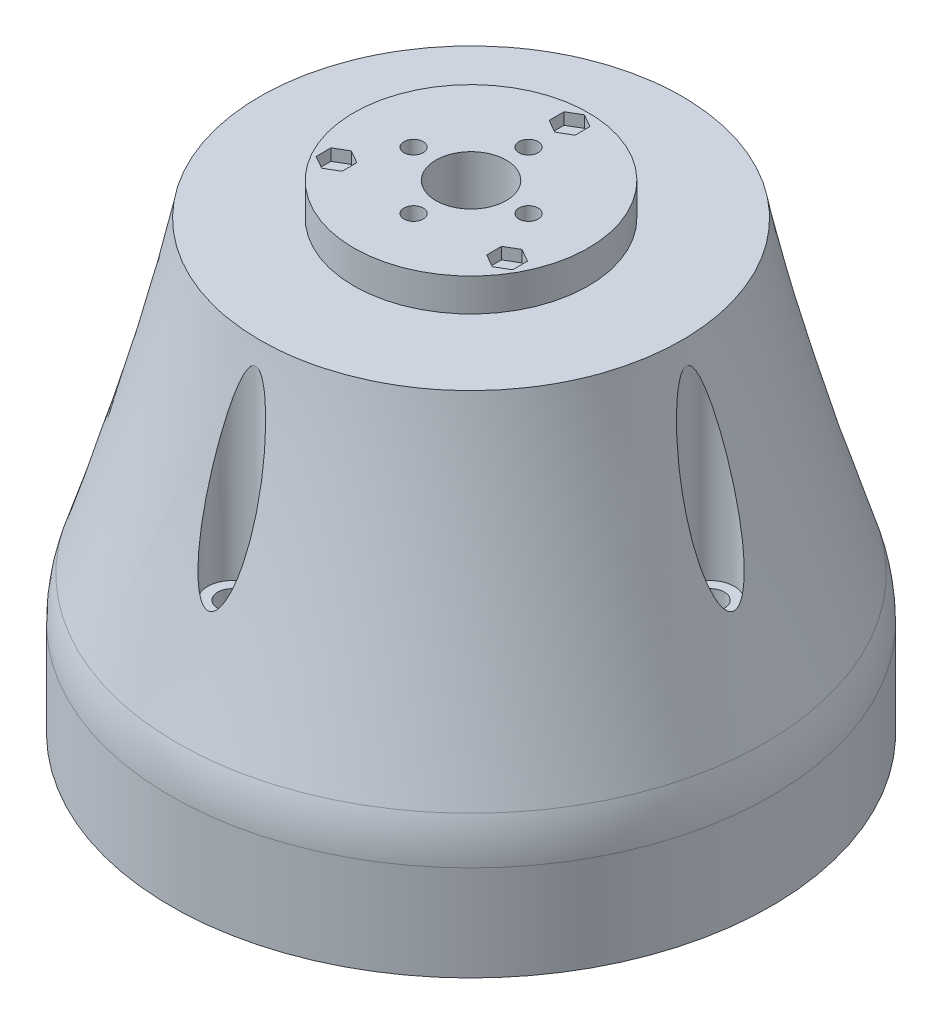
SolidWorks part; units mm, degrees
ref_plane "Front Plane" through (0, 0, 0) normal (0, 0, 1) x (1, 0, 0)
ref_plane "Top Plane" through (0, 0, 0) normal (0, 1, 0) x (1, 0, 0)
ref_plane "Right Plane" through (0, 0, 0) normal (1, 0, 0) x (0, 0, -1)
sketch "Sketch3" plane through (0, 0, 0) normal (0, 1, 0) x (1, 0, 0)
  circle A0 centre (0, 0) radius 64
  dimension "D1" = 128
extrude "Boss-Extrude1" add sketch "Sketch3" along normal blind 15
ref_plane "Plane1" through (0, 85, 0) normal (0, 1, 0) x (1, 0, 0)
sketch "Sketch4" plane through (0, 85, 0) normal (0, 1, 0) x (1, 0, 0)
  circle A0 centre (0, 0) radius 45
  dimension "D1" = 90
sketch "Sketch5" plane through (0, 15, 0) normal (0, 1, 0) x (1, 0, 0)
  circle A1 centre (0, 0) radius 64
  circle A2 centre (0, 0) radius 64
  dimension "D1" = 0
loft "Loft1" add profiles "Sketch5", "Sketch4" connector at (-2.5729, 15, 63.9483) connector at (15.8799, 85, 42.105)
fillet "Fillet1" radius 30 1 edges at (0, 15, 64) type face fillet first side face at (0, 15, 64) second side face at (0, 15, 64)
sketch "Sketch6" plane through (0, 85, 0) normal (0, 1, 0) x (1, 0, 0)
  circle A0 centre (0, 0) radius 51 construction
  circle A1 centre (0, 51) radius 3
  circle A2 centre (51, 0) radius 3
  circle A3 centre (0, -51) radius 3
  circle A4 centre (-51, 0) radius 3
  point P14 (0, 0)
  dimension "D1" = 102
  dimension "D2" = 6
  dimension "D3" = 4
extrude "Cut-Extrude1" cut sketch "Sketch6" against normal blind 85
sketch "Sketch8" plane through (0, 85, 0) normal (0, 1, 0) x (1, 0, 0)
  circle A0 centre (-51, 0) radius 5.11
  circle A1 centre (0, 51) radius 5.11
  circle A2 centre (51, 0) radius 5.11
  circle A3 centre (0, -51) radius 5.11
  point P12 (0, 0)
  dimension "D1" = 10.22
  dimension "D2" = 4
extrude "Cut-Extrude3" cut sketch "Sketch8" against normal blind 45
sketch "Sketch9" plane through (0, 0, 0) normal (0, -1, 0) x (1, 0, 0)
  arc A0 (-16.4684, 53.5238) -> (-53.5238, 16.4684) centre (0, 0) ccw
  arc A1 (-7.1314, 48.6777) -> (7.1314, 48.6777) centre (0, 51) ccw
  arc A5 (-7.1314, 48.6777) -> (-16.4684, 53.5238) centre (-14.2628, 46.3554) ccw
  arc A6 (16.4684, 53.5238) -> (7.1314, 48.6777) centre (14.2628, 46.3554) ccw
  arc A7 (48.6777, 7.1314) -> (53.5238, 16.4684) centre (46.3554, 14.2628) ccw
  arc A8 (48.6777, 7.1314) -> (48.6777, -7.1314) centre (51, 0) ccw
  arc A9 (53.5238, -16.4684) -> (48.6777, -7.1314) centre (46.3554, -14.2628) ccw
  arc A10 (7.1314, -48.6777) -> (16.4684, -53.5238) centre (14.2628, -46.3554) ccw
  arc A11 (7.1314, -48.6777) -> (-7.1314, -48.6777) centre (0, -51) ccw
  arc A12 (-16.4684, -53.5238) -> (-7.1314, -48.6777) centre (-14.2628, -46.3554) ccw
  arc A13 (-48.6777, -7.1314) -> (-53.5238, -16.4684) centre (-46.3554, -14.2628) ccw
  arc A14 (-48.6777, -7.1314) -> (-48.6777, 7.1314) centre (-51, 0) ccw
  arc A15 (-53.5238, 16.4684) -> (-48.6777, 7.1314) centre (-46.3554, 14.2628) ccw
  arc A16 (53.5238, 16.4684) -> (16.4684, 53.5238) centre (0, 0) ccw
  arc A17 (16.4684, -53.5238) -> (53.5238, -16.4684) centre (0, 0) ccw
  arc A18 (-53.5238, -16.4684) -> (-16.4684, -53.5238) centre (0, 0) ccw
  point P15 (0, 0)
  point P35 (0, 0)
  dimension "D1" = 112
  dimension "D2" = 15
  dimension "D3" = 4
  dimension "D4" = 15
  dimension "D5" = 15
extrude "Cut-Extrude4" cut sketch "Sketch9" against normal blind 12
sketch "Sketch17" plane through (0, 12, 0) normal (0, -1, 0) x (1, 0, 0)
  circle A0 centre (0, 0) radius 37.5
  dimension "D1" = 75
extrude "Cut-Extrude10" cut sketch "Sketch17" against normal blind 69
sketch "Sketch19" plane through (0, 0, 0) normal (0, -1, 0) x (1, 0, 0)
  arc A0 (16.4684, -53.5238) -> (53.5238, -16.4684) centre (0, 0) ccw construction
  circle A1 centre (0, 0) radius 64
  circle A2 centre (0, 0) radius 64
  arc A3 (53.5238, -16.4684) -> (48.6777, -7.1314) centre (46.3554, -14.2628) ccw construction
  arc A4 (48.6777, 7.1314) -> (48.6777, -7.1314) centre (51, 0) ccw construction
  arc A5 (48.6777, 7.1314) -> (53.5238, 16.4684) centre (46.3554, 14.2628) ccw construction
  arc A6 (53.5238, 16.4684) -> (16.4684, 53.5238) centre (0, 0) ccw construction
  arc A7 (-7.1314, 48.6777) -> (7.1314, 48.6777) centre (0, 51) ccw construction
  arc A8 (-7.1314, 48.6777) -> (-16.4684, 53.5238) centre (-14.2628, 46.3554) ccw construction
  arc A9 (16.4684, -53.5238) -> (53.5238, -16.4684) centre (0, 0) ccw
  arc A10 (53.5238, -16.4684) -> (48.6777, -7.1314) centre (46.3554, -14.2628) ccw
  arc A11 (48.6777, 7.1314) -> (48.6777, -7.1314) centre (51, 0) ccw
  arc A12 (48.6777, 7.1314) -> (53.5238, 16.4684) centre (46.3554, 14.2628) ccw
  arc A13 (53.5238, 16.4684) -> (16.4684, 53.5238) centre (0, 0) ccw
  arc A14 (-7.1314, 48.6777) -> (7.1314, 48.6777) centre (0, 51) ccw
  arc A15 (-7.1314, 48.6777) -> (-16.4684, 53.5238) centre (-14.2628, 46.3554) ccw
  arc A18 (16.4684, 53.5238) -> (7.1314, 48.6777) centre (14.2628, 46.3554) ccw
  arc A19 (-7.1314, 48.6777) -> (7.1314, 48.6777) centre (0, 51) ccw
  arc A20 (-7.1314, 48.6777) -> (-16.4684, 53.5238) centre (-14.2628, 46.3554) ccw
  arc A21 (-16.4684, 53.5238) -> (-53.5238, 16.4684) centre (0, 0) ccw
  arc A22 (-53.5238, 16.4684) -> (-48.6777, 7.1314) centre (-46.3554, 14.2628) ccw
  arc A23 (-48.6777, -7.1314) -> (-48.6777, 7.1314) centre (-51, 0) ccw
  arc A24 (-48.6777, -7.1314) -> (-53.5238, -16.4684) centre (-46.3554, -14.2628) ccw
  arc A25 (-53.5238, -16.4684) -> (-16.4684, -53.5238) centre (0, 0) ccw
  arc A26 (-16.4684, -53.5238) -> (-7.1314, -48.6777) centre (-14.2628, -46.3554) ccw
  arc A27 (7.1314, -48.6777) -> (-7.1314, -48.6777) centre (0, -51) ccw
  arc A28 (7.1314, -48.6777) -> (16.4684, -53.5238) centre (14.2628, -46.3554) ccw
  arc A29 (16.4684, -53.5238) -> (53.5238, -16.4684) centre (0, 0) ccw
  arc A30 (53.5238, -16.4684) -> (48.6777, -7.1314) centre (46.3554, -14.2628) ccw
  arc A31 (48.6777, 7.1314) -> (48.6777, -7.1314) centre (51, 0) ccw
  arc A32 (48.6777, 7.1314) -> (53.5238, 16.4684) centre (46.3554, 14.2628) ccw
  arc A33 (53.5238, 16.4684) -> (16.4684, 53.5238) centre (0, 0) ccw
  arc A34 (16.4684, 53.5238) -> (7.1314, 48.6777) centre (14.2628, 46.3554) ccw
  arc A35 (-7.1314, 48.6777) -> (7.1314, 48.6777) centre (0, 51) ccw
  arc A36 (-7.1314, 48.6777) -> (-16.4684, 53.5238) centre (-14.2628, 46.3554) ccw
  arc A37 (-16.4684, 53.5238) -> (-53.5238, 16.4684) centre (0, 0) ccw
  arc A38 (-53.5238, 16.4684) -> (-48.6777, 7.1314) centre (-46.3554, 14.2628) ccw
  arc A39 (-48.6777, -7.1314) -> (-48.6777, 7.1314) centre (-51, 0) ccw
  arc A40 (-48.6777, -7.1314) -> (-53.5238, -16.4684) centre (-46.3554, -14.2628) ccw
  arc A41 (-53.5238, -16.4684) -> (-16.4684, -53.5238) centre (0, 0) ccw
  arc A42 (-16.4684, -53.5238) -> (-7.1314, -48.6777) centre (-14.2628, -46.3554) ccw
  arc A43 (7.1314, -48.6777) -> (-7.1314, -48.6777) centre (0, -51) ccw
  arc A44 (7.1314, -48.6777) -> (16.4684, -53.5238) centre (14.2628, -46.3554) ccw
  arc A45 (16.4684, -53.5238) -> (53.5238, -16.4684) centre (0, 0) ccw
  arc A46 (53.5238, -16.4684) -> (48.6777, -7.1314) centre (46.3554, -14.2628) ccw
  arc A47 (48.6777, 7.1314) -> (48.6777, -7.1314) centre (51, 0) ccw
  arc A48 (48.6777, 7.1314) -> (53.5238, 16.4684) centre (46.3554, 14.2628) ccw
  arc A49 (53.5238, 16.4684) -> (16.4684, 53.5238) centre (0, 0) ccw
  circle M19 centre (0, -51) radius 3
  circle M20 centre (51, 0) radius 3
  circle M21 centre (0, 51) radius 3
  circle M22 centre (-51, 0) radius 3
  circle M23 centre (0, 0) radius 64
  arc M24 (-7.1314, 48.6777) -> (7.1314, 48.6777) centre (0, 51) ccw
  arc M25 (7.1314, 48.6777) -> (16.4684, 53.5238) centre (14.2628, 46.3554) cw
  arc M26 (16.4684, 53.5238) -> (53.5238, 16.4684) centre (0, 0) cw
  arc M27 (53.5238, 16.4684) -> (48.6777, 7.1314) centre (46.3554, 14.2628) cw
  arc M28 (48.6777, 7.1314) -> (48.6777, -7.1314) centre (51, 0) ccw
  arc M29 (48.6777, -7.1314) -> (53.5238, -16.4684) centre (46.3554, -14.2628) cw
  arc M30 (53.5238, -16.4684) -> (16.4684, -53.5238) centre (0, 0) cw
  arc M31 (16.4684, -53.5238) -> (7.1314, -48.6777) centre (14.2628, -46.3554) cw
  arc M32 (7.1314, -48.6777) -> (-7.1314, -48.6777) centre (0, -51) ccw
  arc M33 (-7.1314, -48.6777) -> (-16.4684, -53.5238) centre (-14.2628, -46.3554) cw
  arc M34 (-16.4684, -53.5238) -> (-53.5238, -16.4684) centre (0, 0) cw
  arc M35 (-53.5238, -16.4684) -> (-48.6777, -7.1314) centre (-46.3554, -14.2628) cw
  arc M36 (-48.6777, -7.1314) -> (-48.6777, 7.1314) centre (-51, 0) ccw
  arc M37 (-48.6777, 7.1314) -> (-53.5238, 16.4684) centre (-46.3554, 14.2628) cw
  arc M38 (-53.5238, 16.4684) -> (-16.4684, 53.5238) centre (0, 0) cw
  arc M39 (-16.4684, 53.5238) -> (-7.1314, 48.6777) centre (-14.2628, 46.3554) cw
  dimension "D1" = 0
  dimension "D2" = 0
extrude "Boss-Extrude3" add sketch "Sketch19" along normal blind 10 contours M23 M20 M22 M39 M24 M25 M26 M27 M28 M29 M30 M31 M32 M33 M34 M35 M36 M37 M38 M21 M19 region at (-62.1898, 0, 0)
sketch "Sketch21" plane through (0, 85, 0) normal (0, 1, 0) x (1, 0, 0)
  circle A0 centre (0, 0) radius 25
  dimension "D1" = 50
extrude "Boss-Extrude4" add sketch "Sketch21" along normal blind 7
sketch "Sketch20" plane through (0, 92, 0) normal (0, 1, 0) x (1, 0, 0)
  circle A0 centre (0, 0) radius 12.25 construction
  circle A1 centre (0, 0) radius 7.5
  circle A2 centre (0, 12.25) radius 2.05
  circle A3 centre (12.25, 0) radius 2.05
  circle A4 centre (0, -12.25) radius 2.05
  circle A5 centre (-12.25, 0) radius 2.05
  point P15 (0, 0)
  dimension "D1" = 24.5
  dimension "D2" = 15
  dimension "D3" = 4.1
  dimension "D4" = 4
extrude "Cut-Extrude11" cut sketch "Sketch20" against normal up to surface (11 mm away) up to face at (0, 81, -37.5)
sketch "Sketch22" plane through (0, 92, 0) normal (0, 1, 0) x (1, 0, 0)
  line L0 (15.445, -12.1023) -> (18.2034, -13.6754)
  line L1 (2.7584, 19.4269) -> (2.7415, 22.6023)
  line L2 (2.7415, 22.6023) -> (-0.0169, 24.1754)
  line L3 (-0.0169, 24.1754) -> (-2.7584, 22.5731)
  line L4 (-2.7584, 22.5731) -> (-2.7415, 19.3977)
  line L5 (-2.7415, 19.3977) -> (0.0169, 17.8246)
  line L6 (0.0169, 17.8246) -> (2.7584, 19.4269)
  line L7 (15.4281, -8.9269) -> (15.445, -12.1023)
  line L8 (18.1697, -7.3246) -> (15.4281, -8.9269)
  line L9 (20.9281, -8.8977) -> (18.1697, -7.3246)
  line L10 (20.9449, -12.0731) -> (20.9281, -8.8977)
  line L11 (18.2034, -13.6754) -> (20.9449, -12.0731)
  line L12 (-18.2034, -7.3246) -> (-20.9449, -8.9269)
  line L13 (-15.445, -8.8977) -> (-18.2034, -7.3246)
  line L14 (-15.4281, -12.0731) -> (-15.445, -8.8977)
  line L15 (-18.1697, -13.6754) -> (-15.4281, -12.0731)
  line L16 (-20.9281, -12.1023) -> (-18.1697, -13.6754)
  line L17 (-20.9449, -8.9269) -> (-20.9281, -12.1023)
  circle A0 centre (0, 21) radius 2.75 construction
  point P10 (-2.75, 20.9854)
  point P25 (0, 0)
  dimension "D1" = 21
  dimension "D2" = 5.5
  dimension "D4" = 3
extrude "Cut-Extrude12" cut sketch "Sketch22" against normal blind 2.5
sketch "Sketch23" plane through (0, 12, 0) normal (0, -1, 0) x (1, 0, 0)
  line L0 (0, 0) -> (30.052, 30.052) construction
  line L1 (0, 0) -> (0, 42.5)
  circle A1 centre (0, 0) radius 42.5 construction
  circle A2 centre (30.052, 30.052) radius 1.55
  circle A3 centre (10.9998, -41.0518) radius 1.55
  circle A4 centre (-41.0518, 10.9998) radius 1.55
  point P5 (0, 0)
  point P13 (0, 0)
  dimension "D1" = 45
  dimension "D2" = 85
  dimension "D3" = 3.1
  dimension "D4" = 3
extrude "Cut-Extrude13" cut sketch "Sketch23" against normal blind 10 contours A2 | A3 | A4 region at (30.052, 12, 30.052) region at (10.9998, 12, -41.0518) region at (-41.0518, 12, 10.9998)
